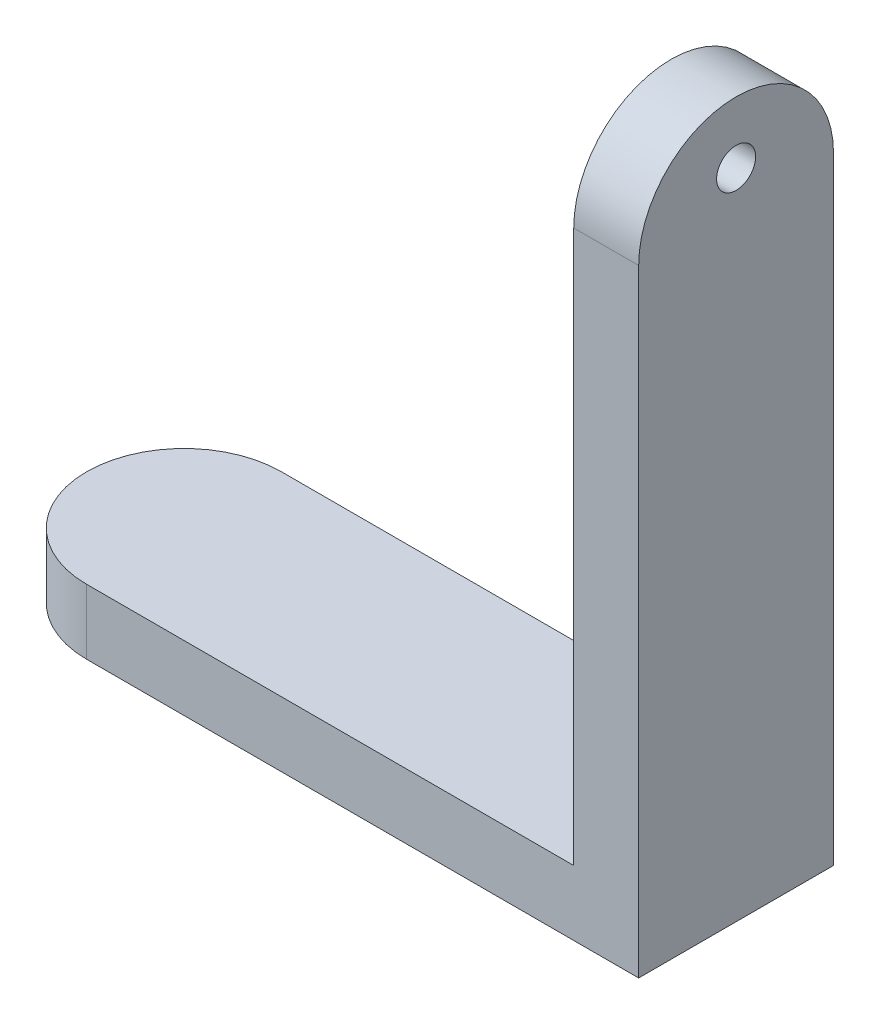
SolidWorks part; units mm, degrees
ref_plane "Front Plane" through (0, 0, 0) normal (0, 0, 1) x (1, 0, 0)
ref_plane "Top Plane" through (0, 0, 0) normal (0, 1, 0) x (1, 0, 0)
ref_plane "Right Plane" through (0, 0, 0) normal (1, 0, 0) x (0, 0, -1)
sketch "Sketch1" plane through (0, 0, 0) normal (0, 1, 0) x (1, 0, 0)
  line L1 (12.7, -3.81) -> (-12.7, -3.81)
  line L2 (12.7, -3.81) -> (12.7, 3.81)
  line L3 (12.7, 3.81) -> (-12.7, 3.81)
  line L4 (-12.7, -3.81) -> (-12.7, 3.81)
  line L5 (12.7, -3.81) -> (-12.7, 3.81) construction
  line L6 (12.7, 3.81) -> (-12.7, -3.81) construction
  point P0 (0, 0)
extrude "Boss-Extrude1" add sketch "Sketch1" along normal blind 2.54
sketch "Sketch3" plane through (0, 2.54, 0) normal (0, 1, 0) x (1, 0, 0)
  line L0 (12.7, 3.81) -> (-12.7, 3.81) construction
  line L1 (12.7, -3.81) -> (10.16, -3.81)
  line L2 (12.7, -3.81) -> (12.7, 3.81)
  line L3 (12.7, 3.81) -> (10.16, 3.81)
  line L4 (10.16, -3.81) -> (10.16, 3.81)
extrude "Boss-Extrude3" add sketch "Sketch3" along normal blind 25.4
fillet "Fillet1" 2 edges at (-12.7, 1.27, 3.81) (-12.7, 1.27, -3.81) type full round first side face at (3.3867, 10.16, 3.81) second side face at (3.3867, 10.16, -3.81) middle face at (-12.7, 1.27, 0)
sketch "Sketch5" plane through (10.16, 0, 0) normal (-1, 0, 0) x (0, 0, 1)
  circle A0 centre (0, 25.5317) radius 0.762
extrude "Cut-Extrude1" cut sketch "Sketch5" against normal blind 25.4
fillet "Fillet2" 2 edges at (11.43, 27.94, -3.81) (11.43, 27.94, 3.81) type full round first side face at (4.6567, 10.16, -3.81) second side face at (4.6567, 10.16, 3.81) middle face at (11.43, 27.94, 0)
